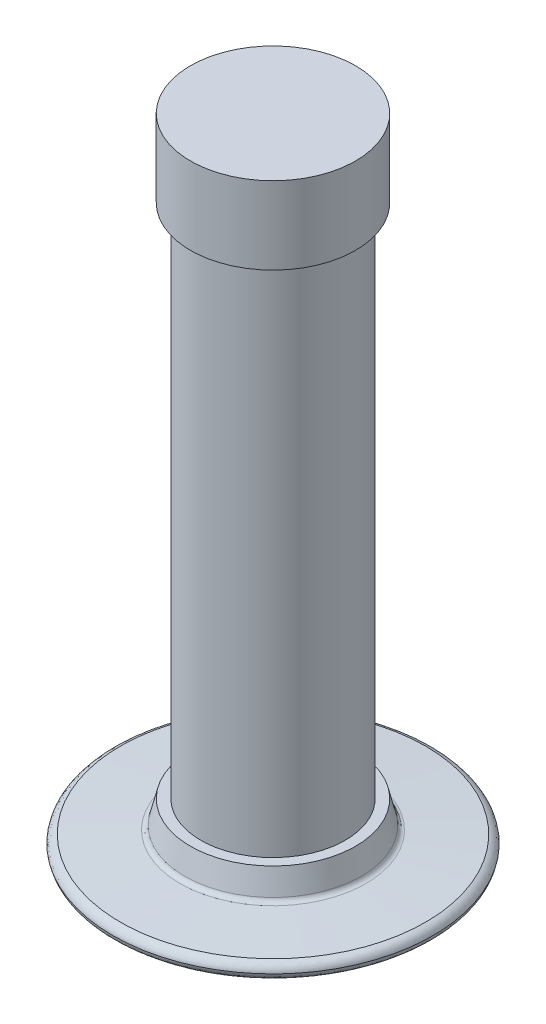
SolidWorks part; units mm, degrees
ref_plane "Front Plane" through (0, 0, 0) normal (0, 0, 1) x (1, 0, 0)
ref_plane "Top Plane" through (0, 0, 0) normal (0, 1, 0) x (1, 0, 0)
ref_plane "Right Plane" through (0, 0, 0) normal (1, 0, 0) x (0, 0, -1)
sketch "Sketch1" plane through (0, 0, 0) normal (0, 0, 1) x (1, 0, 0)
  line L0 (0, 0) -> (0, 130)
  line L1 (0, 130) -> (16, 130)
  line L2 (16, 130) -> (16, 115)
  line L3 (16, 115) -> (14, 115)
  line L4 (14, 15) -> (14, 115)
  line L5 (0, 0) -> (16, 0)
  line L6 (16, 0) -> (16, 15) construction
  line L7 (16, 7.5) -> (31, 7.5) construction
  line L8 (16, 0) -> (17.1117, 4.4876)
  line L9 (18.0203, 5.2452) -> (29.5645, 5.9633)
  line L10 (18.0203, 9.7548) -> (29.5645, 9.0367)
  line L11 (16, 15) -> (17.1117, 10.5124)
  line L12 (16, 15) -> (14, 15)
  arc A0 (18.0203, 5.2452) -> (17.1117, 4.4876) centre (18.0824, 4.2471) ccw
  arc A1 (18.0203, 9.7548) -> (17.1117, 10.5124) centre (18.0824, 10.7529) cw
  spline S0 degree 2 poles (29.5645, 5.9633) (30.8531, 6.3859) (31, 7.5) knots 0 0 0 1 1 1
  spline S1 degree 2 poles (29.5645, 9.0367) (30.8531, 8.6141) (31, 7.5) knots 0 0 0 1 1 1
  dimension "D8" = 1
  dimension "D1" = 130
  dimension "D2" = 16
  dimension "D3" = 15
  dimension "D4" = 2
  dimension "D5" = 15
  dimension "D6" = 16
  dimension "D7" = 15
  dimension "D9" = 2
revolve "Revolve1" add sketch "Sketch1" angle 360 about L0
